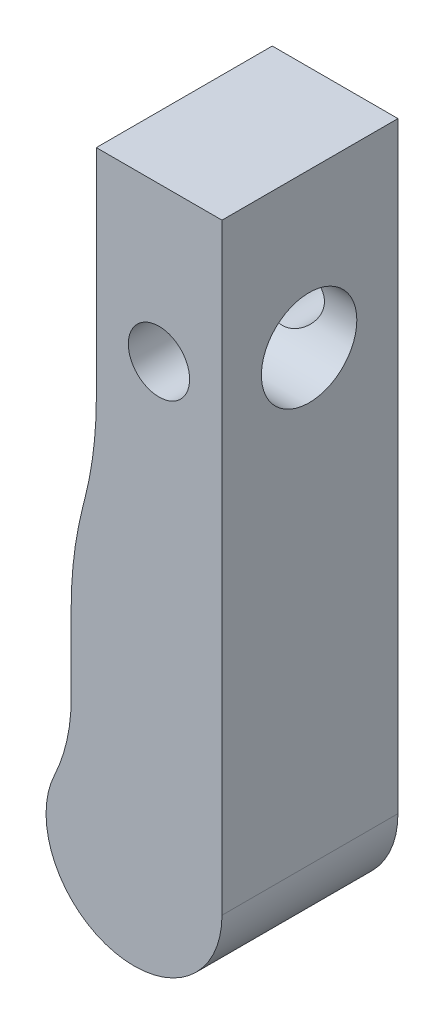
SolidWorks part; units mm, degrees
ref_plane "Plan de face" through (0, 0, 0) normal (0, 0, 1) x (1, 0, 0)
ref_plane "Plan de dessus" through (0, 0, 0) normal (0, 1, 0) x (1, 0, 0)
ref_plane "Plan de droite" through (0, 0, 0) normal (1, 0, 0) x (0, 0, -1)
sketch "Esquisse1" plane through (0, 0, 0) normal (0, 0, 1) x (1, 0, 0)
  line L2 (-5, 0) -> (-5, -10.5)
  line L5 (-5, 0) -> (0, 0)
  line L10 (-6, -14.5) -> (-6, -21.5)
  line L13 (-6, -14.5) -> (-5, -10.5)
  line L14 (-3.5, -23.9495) -> (0, -23.9495) construction
  line L15 (0, 0) -> (0, -23.9495)
  arc A1 (-6, -21.5) -> (0, -23.9495) centre (-3.5, -23.9495) ccw
  dimension "D5" = 7
  dimension "D1" = 5
  dimension "D2" = 10.5
  dimension "D3" = 4
  dimension "D4" = 1
  dimension "D6" = 7
  dimension "D8" = 3.5
  dimension "D9" = 3.5
extrude "Boss.-Extru.2" add sketch "Esquisse1" along normal blind 7 contours L13 L2 L5 L15 A1 L10
fillet "Congé1" radius 7 1 edges at (-6, -21.5, 3.5)
fillet "Congé2" radius 15 2 edges at (-6, -14.5, 3.5) (-5, -10.5, 3.5)
sketch "Esquisse4" plane through (0, 0, 7) normal (0, 0, 1) x (1, 0, 0)
  point P0 (-2.5076, -6.1279)
hole_wizard "Dégagement #21" positions "Esquisse4" profile "Esquisse3" hole size "#2" standard "Ansi Inch" end condition through all
sketch "Esquisse3" plane through (-2.5076, -6.1279, 7) normal (1, 0, 0) x (0, -1, 0)
  line L0 (0, 0) -> (0, 7)
  line L1 (0, 7) -> (1.2192, 7)
  line L2 (1.2192, 7) -> (1.2192, 0)
  line L5 (1.2192, 0) -> (0, 0)
  line L11 (0, -6.35) -> (0, 107.95) construction
  dimension "Diamètre du perçage jusqu'au prochain" = 2.4384
  dimension "Profondeur du perçage jusqu'au prochain" = 7
sketch "Esquisse7" plane through (0, 0, 0) normal (1, 0, 0) x (0, 0, -1)
  point P0 (-3.5342, -6.1279)
hole_wizard "Dégagement #61" positions "Esquisse7" profile "Esquisse6" hole size "#6" standard "Ansi Inch" end condition through all
sketch "Esquisse6" plane through (0, -6.1279, 3.5342) normal (0, 1, 0) x (0, 0, -1)
  line L0 (0, 0) -> (0, 7)
  line L1 (0, 7) -> (1.8986, 7)
  line L2 (1.8986, 7) -> (1.8986, 0)
  line L5 (1.8986, 0) -> (0, 0)
  line L11 (0, -6.35) -> (0, 107.95) construction
  dimension "Diamètre du perçage jusqu'au prochain" = 3.7973
  dimension "Profondeur du perçage jusqu'au prochain" = 7
